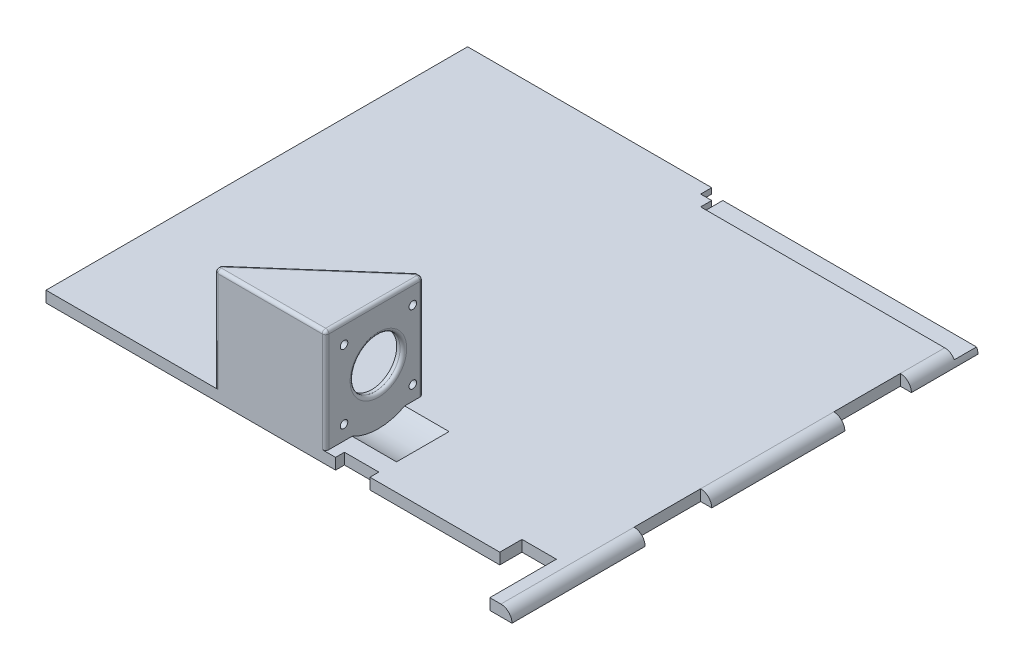
SolidWorks part; units mm, degrees
ref_plane "前基準面" through (0, 0, 0) normal (0, 0, 1) x (1, 0, 0)
ref_plane "上基準面" through (0, 0, 0) normal (0, 1, 0) x (1, 0, 0)
ref_plane "右基準面" through (0, 0, 0) normal (1, 0, 0) x (0, 0, -1)
sketch "草圖1" plane through (0, 0, 0) normal (0, 1, 0) x (1, 0, 0)
  line L0 (-36.2537, 43.5351) -> (203.7463, 43.5351)
  line L1 (203.7463, 43.5351) -> (203.7463, -286.4649)
  line L2 (198.7463, -286.4649) -> (198.7463, -256.4649)
  line L3 (198.7463, -256.4649) -> (183.2463, -256.4649)
  line L4 (183.2463, -256.4649) -> (183.2463, -266.4649)
  line L5 (183.2463, -266.4649) -> (124.7463, -266.4649)
  line L6 (124.7463, -266.4649) -> (124.7463, -262.4649)
  line L7 (124.7463, -262.4649) -> (109.2463, -262.4649)
  line L8 (109.2463, -262.4649) -> (109.2463, -266.4649)
  line L9 (109.2463, -266.4649) -> (-21.2537, -266.4649)
  line L10 (-21.2537, -266.4649) -> (-21.2537, 38.5351)
  line L11 (-21.2537, 38.5351) -> (-36.2537, 38.5351)
  line L12 (-36.2537, 38.5351) -> (-36.2537, 43.5351)
  line L13 (198.7463, -286.4649) -> (203.7463, -286.4649)
  line L15 (203.7463, -286.4649) -> (208.7463, -286.4649)
  line L16 (203.7463, -286.4649) -> (203.7463, -226.4649)
  line L17 (203.7463, -226.4649) -> (208.7463, -226.4649)
  line L18 (208.7463, -286.4649) -> (208.7463, -226.4649)
  line L19 (-36.2537, 43.5351) -> (-6.2537, 43.5351)
  line L20 (-36.2537, 43.5351) -> (-36.2537, 48.5351)
  line L21 (-36.2537, 48.5351) -> (-6.2537, 48.5351)
  line L22 (-6.2537, 43.5351) -> (-6.2537, 48.5351)
  line L23 (203.7463, 43.5351) -> (173.7463, 43.5351)
  line L24 (203.7463, 43.5351) -> (203.7463, 48.5351)
  line L25 (203.7463, 48.5351) -> (173.7463, 48.5351)
  line L26 (173.7463, 43.5351) -> (173.7463, 48.5351)
  line L27 (203.7463, 43.5351) -> (208.7463, 43.5351)
  line L28 (203.7463, 43.5351) -> (203.7463, -16.4649)
  line L29 (203.7463, -16.4649) -> (208.7463, -16.4649)
  line L30 (208.7463, 43.5351) -> (208.7463, -16.4649)
  line L31 (83.7463, 43.5351) -> (98.7463, 43.5351)
  line L32 (83.7463, 43.5351) -> (83.7463, 48.5351)
  line L33 (83.7463, 48.5351) -> (98.7463, 48.5351)
  line L34 (98.7463, 43.5351) -> (98.7463, 48.5351)
  line L35 (83.7463, 43.5351) -> (68.7463, 43.5351)
  line L36 (83.7463, 43.5351) -> (83.7463, 48.5351)
  line L37 (83.7463, 48.5351) -> (68.7463, 48.5351)
  line L38 (68.7463, 43.5351) -> (68.7463, 48.5351)
  line L39 (203.7463, -46.4649) -> (208.7463, -46.4649)
  line L40 (203.7463, -46.4649) -> (203.7463, -106.4649)
  line L41 (203.7463, -106.4649) -> (208.7463, -106.4649)
  line L42 (208.7463, -46.4649) -> (208.7463, -106.4649)
  line L43 (203.7463, -136.4649) -> (208.7463, -136.4649)
  line L44 (203.7463, -136.4649) -> (203.7463, -196.4649)
  line L45 (203.7463, -196.4649) -> (208.7463, -196.4649)
  line L46 (208.7463, -136.4649) -> (208.7463, -196.4649)
  dimension "D3" = 5
  dimension "D1" = 240
  dimension "D2" = 330
  dimension "D4" = 15
  dimension "D5" = 130.5
  dimension "D6" = 4
  dimension "D7" = 4
  dimension "D8" = 15.5
  dimension "D9" = 58.5
  dimension "D10" = 10
  dimension "D11" = 15.5
  dimension "D12" = 30
  dimension "D13" = 5
  dimension "D14" = 60
  dimension "D15" = 5
  dimension "D16" = 5
  dimension "D17" = 30
  dimension "D18" = 5
  dimension "D19" = 30
  dimension "D20" = 60
  dimension "D21" = 5
  dimension "D22" = 5
  dimension "D23" = 15
  dimension "D24" = 5
  dimension "D25" = 15
  dimension "D26" = 60
  dimension "D27" = 5
  dimension "D28" = 30
  dimension "D29" = 60
  dimension "D30" = 5
  dimension "D31" = 30
  dimension "D32" = 30
extrude "填料-伸長1" add sketch "草圖1" along normal blind 5 contours L2 L13 L1 L0 L12 L11 L10 L9 L8 L7 L6 L5 L4 L3 | L15 L18 L17 L1 | L30 L27 L1 L29 | L26 L0 L24 L25 | L0 L22 L21 L20 | L32 L33 L34 L31 | L36 L37 L38 L35 | L46 L45 L44 L43 | L42 L41 L40 L39 region at (-21.2537, 0, -46.0351) region at (91.0303, 0, 111.0679) region at (188.7463, 0, -46.0351) region at (206.2463, 0, -13.5351) region at (206.2463, 0, 256.4649)
fillet "圓角1" radius 5 4 edges at (208.7463, 5, -13.5351) (208.7463, 5, 76.4649) (208.7463, 5, 166.4649) (208.7463, 5, 256.4649)
sketch "草圖2" plane through (0, 5, 0) normal (0, 1, 0) x (1, 0, 0)
  line L1 (-36.2537, 48.5351) -> (208.7463, 48.5351)
  line L2 (-36.2537, 48.5351) -> (-36.2537, -76.4649)
  line L3 (-36.2537, -76.4649) -> (208.7463, -76.4649)
  line L4 (208.7463, 48.5351) -> (208.7463, -76.4649)
  dimension "D1" = 125
extrude "除料-伸長1" cut sketch "草圖2" against normal blind 5
sketch "草圖3" plane through (0, 0, 76.4649) normal (0, 0, -1) x (-1, 0, 0)
  line L1 (21.2537, 0) -> (-88.7463, 0)
  line L2 (21.2537, 0) -> (21.2537, 2.5)
  line L3 (21.2537, 2.5) -> (-88.7463, 2.5)
  line L4 (-88.7463, 0) -> (-88.7463, 2.5)
  line L5 (-93.7463, 2.5) -> (-208.7463, 2.5)
  line L6 (-93.7463, 2.5) -> (-93.7463, 5)
  line L7 (-93.7463, 5) -> (-208.7463, 5)
  line L8 (-208.7463, 2.5) -> (-208.7463, 5)
  point P9 (-93.7463, 3.75)
  dimension "D1" = 2.5
  dimension "D2" = 110
  dimension "D3" = 2.5
  dimension "D4" = 115
  dimension "D5" = 5
extrude "除料-伸長2" cut sketch "草圖3" against normal blind 10
sketch "草圖4" plane through (0, 0, 76.4649) normal (0, 0, -1) x (-1, 0, 0)
  line L1 (-93.7463, 5) -> (-88.7463, 5)
  line L2 (-93.7463, 5) -> (-93.7463, 0)
  line L3 (-93.7463, 0) -> (-88.7463, 0)
  line L4 (-88.7463, 5) -> (-88.7463, 0)
extrude "除料-伸長3" cut sketch "草圖4" against normal blind 5
sketch "草圖5" plane through (0, 0, 266.4649) normal (0, 0, 1) x (1, 0, 0)
  line L0 (109.2463, 5) -> (-21.2537, 5) construction
  line L1 (104.7463, 5) -> (54.7463, 5)
  line L2 (104.7463, 5) -> (104.7463, 51.65)
  line L3 (104.7463, 51.65) -> (54.7463, 51.65)
  line L4 (54.7463, 5) -> (54.7463, 51.65)
  line L5 (124.7463, 5) -> (124.7463, 0) construction
  dimension "D1" = 50
  dimension "D2" = 46.65
  dimension "D3" = 20
  dimension "D4" = 0
extrude "填料-伸長2" add sketch "草圖5" against normal blind 47 contours L2 L1 L4 L3
sketch "草圖6" plane through (54.7463, 0, 0) normal (-1, 0, 0) x (0, 0, 1)
  line L0 (219.4649, 51.65) -> (266.4649, 51.65) construction
  line L1 (222.2649, 49.05) -> (263.6649, 49.05)
  line L2 (222.2649, 49.05) -> (222.2649, 5)
  line L3 (222.2649, 5) -> (263.6649, 5)
  line L4 (263.6649, 49.05) -> (263.6649, 5)
  line L5 (219.4649, 5) -> (219.4649, 51.65) construction
  line L6 (266.4649, 5) -> (266.4649, 51.65) construction
  line L7 (266.4649, 5) -> (76.4649, 5) construction
  dimension "D1" = 2.6
  dimension "D2" = 2.8
  dimension "D3" = 2.8
  dimension "D4" = 0
extrude "除料-伸長4" cut sketch "草圖6" against normal blind 47 contours L2 L1 L4 L3
sketch "草圖7" plane through (101.7463, 0, 0) normal (-1, 0, 0) x (0, 0, 1)
  line L0 (263.6649, 49.05) -> (263.6649, 5) construction
  line L1 (222.2649, 49.05) -> (263.6649, 49.05) construction
  line L2 (222.2649, 49.05) -> (222.2649, 5) construction
  line L5 (263.6649, 49.05) -> (263.6649, 5) construction
  circle A0 centre (242.6649, 27.02) radius 11.25
  dimension "D1" = 41.4
  dimension "D4" = 22.5
  dimension "D2" = 21
  dimension "D3" = 22.03
extrude "除料-伸長5" cut sketch "草圖7" against normal through all
sketch "草圖8" plane through (0, 51.65, 0) normal (0, 1, 0) x (1, 0, 0)
  line L4 (54.7463, -263.6649) -> (101.7463, -222.4649)
  line L8 (104.7463, -219.4649) -> (54.7463, -219.4649) construction
  line L9 (54.7463, -263.6649) -> (54.7463, -219.4649)
  line L13 (104.7463, -219.4649) -> (54.7463, -219.4649)
  line L14 (101.7463, -222.4649) -> (104.7463, -222.4649)
  line L15 (104.7463, -219.4649) -> (104.7463, -266.4649) construction
  line L16 (104.7463, -222.4649) -> (104.7463, -219.4649)
  dimension "D2" = 3
extrude "除料-伸長6" cut sketch "草圖8" against normal blind 46.65
sketch "草圖10" plane through (101.7463, 0, 0) normal (-1, 0, 0) x (0, 0, 1)
  circle A0 centre (227.1649, 42.52) radius 1.7
  circle A1 centre (258.1649, 42.52) radius 1.7
  circle A2 centre (258.1649, 11.52) radius 1.7
  circle A3 centre (227.1649, 11.52) radius 1.7
  circle A4 centre (242.6649, 27.02) radius 11.25 construction
  dimension "D1" = 3.4
  dimension "D2" = 3.4
  dimension "D3" = 3.4
  dimension "D4" = 3.4
  dimension "D5" = 15.5
  dimension "D6" = 15.5
  dimension "D7" = 15.5
  dimension "D8" = 15.5
  dimension "D9" = 15.5
  dimension "D10" = 15.5
  dimension "D11" = 15.5
  dimension "D12" = 15.5
extrude "除料-伸長7" cut sketch "草圖10" against normal through all
sketch "草圖13" plane through (104.7463, 0, 0) normal (1, 0, 0) x (0, 0, -1)
  circle A0 centre (-242.6649, 27.02) radius 25
  dimension "D1" = 50
extrude "除料-伸長9" cut sketch "草圖13" along normal blind 20
fillet "圓角11" radius 1.497 9 edges at (104.7463, 51.65, 244.4649) (79.7463, 51.65, 266.4649) (54.7463, 51.65, 265.0649) (78.2463, 51.65, 243.0649) (103.2463, 51.65, 222.4649) (54.7463, 28.325, 266.4649) (104.7463, 28.325, 266.4649) (104.7463, 27.02, 231.4149) (104.7463, 28.325, 222.4649)
equation "\"1.5.0000mm\"=10"
